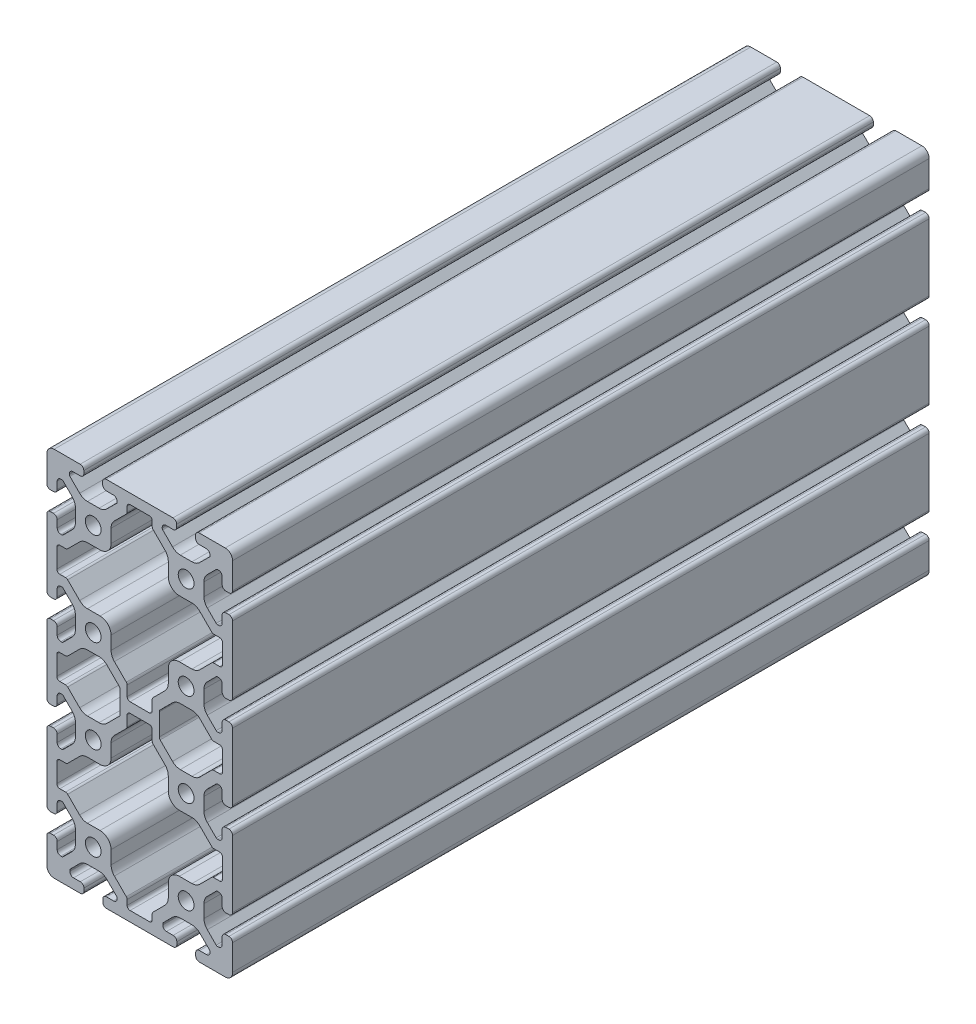
SolidWorks part; units mm, degrees
material "6105-T5 Aluminum"
ref_plane "Front Plane" through (0, 0, 0) normal (0, 0, 1) x (1, 0, 0)
ref_plane "Top Plane" through (0, 0, 0) normal (0, 1, 0) x (1, 0, 0)
ref_plane "Right Plane" through (0, 0, 0) normal (1, 0, 0) x (0, 0, -1)
sketch "Sketch1" plane through (0, 0, 0) normal (0, 0, 1) x (1, 0, 0)
  line L0 (-24.13, 57.84) -> (-15.87, 57.84)
  line L1 (-14.6, 56.57) -> (-14.6, 52.2333)
  line L2 (-14.228, 51.3353) -> (-9.1098, 46.2171)
  line L3 (-7.685, 42.7773) -> (-7.685, 37.065)
  line L4 (-2.935, 32.315) -> (2.5008, 32.315)
  line L5 (5.8595, 30.9238) -> (11.0113, 25.772)
  line L6 (11.9093, 25.4) -> (14.41, 25.4)
  line L7 (15.68, 24.13) -> (15.68, 15.87)
  line L8 (14.41, 14.6) -> (11.9093, 14.6)
  line L9 (11.0113, 14.228) -> (5.8595, 9.0762)
  line L10 (2.5008, 7.685) -> (-2.935, 7.685)
  line L11 (-7.685, 2.935) -> (-7.685, -2.7773)
  line L12 (-9.1098, -6.2171) -> (-14.228, -11.3353)
  line L13 (-14.6, -12.2334) -> (-14.6, -14.41)
  line L14 (-15.87, -15.68) -> (-24.13, -15.68)
  line L15 (-25.4, -14.41) -> (-25.4, -12.2334)
  line L16 (-25.772, -11.3353) -> (-30.8902, -6.2171)
  line L17 (-32.315, -2.7773) -> (-32.315, 2.935)
  line L18 (-37.065, 7.685) -> (-42.5008, 7.685)
  line L19 (-45.8595, 9.0762) -> (-51.0113, 14.228)
  line L20 (-51.9093, 14.6) -> (-54.41, 14.6)
  line L21 (-55.68, 15.87) -> (-55.68, 24.13)
  line L22 (-54.41, 25.4) -> (-51.9093, 25.4)
  line L23 (-51.0113, 25.772) -> (-45.8595, 30.9238)
  line L24 (-42.5008, 32.315) -> (-37.065, 32.315)
  line L25 (-32.315, 37.065) -> (-32.315, 42.7773)
  line L26 (-30.8902, 46.2171) -> (-25.772, 51.3353)
  line L27 (-25.4, 52.2333) -> (-25.4, 56.57)
  line L28 (-28.802, 54.4147) -> (-34.1405, 49.0762)
  line L29 (-37.4992, 47.685) -> (-42.5008, 47.685)
  line L30 (-45.8595, 49.0762) -> (-51.0113, 54.228)
  line L31 (-51.9093, 54.6) -> (-54.41, 54.6)
  line L32 (-55.68, 55.87) -> (-55.68, 64.13)
  line L33 (-54.41, 65.4) -> (-51.9093, 65.4)
  line L34 (-51.0113, 65.772) -> (-45.8595, 70.9238)
  line L35 (-42.5008, 72.315) -> (-37.4992, 72.315)
  line L36 (-34.1405, 70.9238) -> (-28.802, 65.5853)
  line L37 (-28.43, 64.6872) -> (-28.43, 55.3128)
  line L38 (-11.57, 55.3128) -> (-11.57, 64.6872)
  line L39 (-11.198, 65.5853) -> (-5.8595, 70.9238)
  line L40 (-2.5008, 72.315) -> (2.5008, 72.315)
  line L41 (5.8595, 70.9238) -> (11.0113, 65.772)
  line L42 (11.9093, 65.4) -> (14.41, 65.4)
  line L43 (15.68, 64.13) -> (15.68, 55.87)
  line L44 (14.41, 54.6) -> (11.9093, 54.6)
  line L45 (11.0113, 54.228) -> (5.8595, 49.0762)
  line L46 (2.5008, 47.685) -> (-2.5008, 47.685)
  line L47 (-5.8595, 49.0762) -> (-11.198, 54.4147)
  line L48 (-15.87, 62.16) -> (-24.13, 62.16)
  line L49 (-25.4, 63.43) -> (-25.4, 67.7667)
  line L50 (-25.772, 68.6647) -> (-30.8902, 73.7829)
  line L51 (-32.315, 77.2227) -> (-32.315, 82.935)
  line L52 (-37.065, 87.685) -> (-42.5008, 87.685)
  line L53 (-45.8595, 89.0762) -> (-51.0113, 94.228)
  line L54 (-51.9093, 94.6) -> (-54.41, 94.6)
  line L55 (-55.68, 95.87) -> (-55.68, 104.13)
  line L56 (-54.41, 105.4) -> (-51.9093, 105.4)
  line L57 (-51.0113, 105.772) -> (-45.8595, 110.9238)
  line L58 (-42.5008, 112.315) -> (-37.065, 112.315)
  line L59 (-32.315, 117.065) -> (-32.315, 122.7773)
  line L60 (-30.8902, 126.2171) -> (-25.772, 131.3353)
  line L61 (-25.4, 132.2333) -> (-25.4, 134.41)
  line L62 (-24.13, 135.68) -> (-15.87, 135.68)
  line L63 (-14.6, 134.41) -> (-14.6, 132.2333)
  line L64 (-14.228, 131.3353) -> (-9.1098, 126.2171)
  line L65 (-7.685, 122.7773) -> (-7.685, 117.065)
  line L66 (-2.935, 112.315) -> (2.5008, 112.315)
  line L67 (5.8595, 110.9238) -> (11.0113, 105.772)
  line L68 (11.9093, 105.4) -> (14.41, 105.4)
  line L69 (15.68, 104.13) -> (15.68, 95.87)
  line L70 (14.41, 94.6) -> (11.9093, 94.6)
  line L71 (11.0113, 94.228) -> (5.8595, 89.0762)
  line L72 (2.5008, 87.685) -> (-2.935, 87.685)
  line L73 (-7.685, 82.935) -> (-7.685, 77.2227)
  line L74 (-9.1098, 73.7829) -> (-14.228, 68.6647)
  line L75 (-14.6, 67.7667) -> (-14.6, 63.43)
  line L76 (18.43, 115.94) -> (17.0946, 115.94)
  line L77 (15.5246, 114.37) -> (15.5246, 111.285)
  line L78 (13.9546, 109.715) -> (13.4925, 109.715)
  line L79 (12.9551, 109.9376) -> (9.1098, 113.7829)
  line L80 (7.685, 117.2227) -> (7.685, 122.7773)
  line L81 (9.1098, 126.2171) -> (12.9551, 130.0624)
  line L82 (13.4925, 130.285) -> (13.9546, 130.285)
  line L83 (15.5246, 128.715) -> (15.5246, 125.63)
  line L84 (17.0946, 124.06) -> (18.43, 124.06)
  line L85 (20, 125.63) -> (20, 136.83)
  line L86 (16.83, 140) -> (5.63, 140)
  line L87 (4.06, 138.43) -> (4.06, 137.25)
  line L88 (5.63, 135.68) -> (8.7154, 135.68)
  line L89 (10.2854, 134.11) -> (10.2854, 133.6201)
  line L90 (9.947, 133.1637) -> (5.8595, 129.0762)
  line L91 (2.5008, 127.685) -> (-2.5008, 127.685)
  line L92 (-5.8595, 129.0762) -> (-10.0628, 133.2795)
  line L93 (-10.2854, 133.8169) -> (-10.2854, 134.11)
  line L94 (-8.7154, 135.68) -> (-5.63, 135.68)
  line L95 (-4.06, 137.25) -> (-4.06, 138.43)
  line L96 (-5.63, 140) -> (-34.37, 140)
  line L97 (-35.94, 138.43) -> (-35.94, 137.25)
  line L98 (-34.37, 135.68) -> (-31.2846, 135.68)
  line L99 (-29.7146, 134.11) -> (-29.7146, 133.6201)
  line L100 (-30.053, 133.1637) -> (-34.1405, 129.0762)
  line L101 (-37.4992, 127.685) -> (-42.5008, 127.685)
  line L102 (-45.8595, 129.0762) -> (-50.0628, 133.2795)
  line L103 (-50.2854, 133.8169) -> (-50.2854, 134.11)
  line L104 (-48.7154, 135.68) -> (-45.63, 135.68)
  line L105 (-44.06, 137.25) -> (-44.06, 138.43)
  line L106 (-45.63, 140) -> (-56.83, 140)
  line L107 (-60, 136.83) -> (-60, 125.63)
  line L108 (-58.43, 124.06) -> (-57.0946, 124.06)
  line L109 (-55.5246, 125.63) -> (-55.5246, 128.715)
  line L110 (-53.9546, 130.285) -> (-53.4925, 130.285)
  line L111 (-52.9551, 130.0624) -> (-49.1098, 126.2171)
  line L112 (-47.685, 122.7773) -> (-47.685, 117.2227)
  line L113 (-49.1098, 113.7829) -> (-52.9551, 109.9376)
  line L114 (-53.4925, 109.715) -> (-53.9546, 109.715)
  line L115 (-55.5246, 111.285) -> (-55.5246, 114.37)
  line L116 (-57.0946, 115.94) -> (-58.43, 115.94)
  line L117 (-60, 114.37) -> (-60, 85.63)
  line L118 (-58.43, 84.06) -> (-57.0946, 84.06)
  line L119 (-55.5246, 85.63) -> (-55.5246, 88.715)
  line L120 (-53.9546, 90.285) -> (-53.4925, 90.285)
  line L121 (-52.9551, 90.0624) -> (-49.1098, 86.2171)
  line L122 (-47.685, 82.7773) -> (-47.685, 77.2227)
  line L123 (-49.1098, 73.7829) -> (-52.9551, 69.9376)
  line L124 (-53.4925, 69.715) -> (-53.9546, 69.715)
  line L125 (-55.5246, 71.285) -> (-55.5246, 74.37)
  line L126 (-57.0946, 75.94) -> (-58.43, 75.94)
  line L127 (-60, 74.37) -> (-60, 45.63)
  line L128 (-58.43, 44.06) -> (-57.0946, 44.06)
  line L129 (-55.5246, 45.63) -> (-55.5246, 48.715)
  line L130 (-53.9546, 50.285) -> (-53.4925, 50.285)
  line L131 (-52.9551, 50.0624) -> (-49.1098, 46.2171)
  line L132 (-47.685, 42.7773) -> (-47.685, 37.2227)
  line L133 (-49.1098, 33.7829) -> (-52.9551, 29.9376)
  line L134 (-53.4925, 29.715) -> (-53.9546, 29.715)
  line L135 (-55.5246, 31.285) -> (-55.5246, 34.37)
  line L136 (-57.0946, 35.94) -> (-58.43, 35.94)
  line L137 (-60, 34.37) -> (-60, 5.63)
  line L138 (-58.43, 4.06) -> (-57.0946, 4.06)
  line L139 (-55.5246, 5.63) -> (-55.5246, 8.715)
  line L140 (-53.9546, 10.285) -> (-53.4925, 10.285)
  line L141 (-52.9551, 10.0624) -> (-49.1098, 6.2171)
  line L142 (-47.685, 2.7773) -> (-47.685, -2.7773)
  line L143 (-49.1098, -6.2171) -> (-52.9551, -10.0624)
  line L144 (-53.4925, -10.285) -> (-53.9546, -10.285)
  line L145 (-55.5246, -8.715) -> (-55.5246, -5.63)
  line L146 (-57.0946, -4.06) -> (-58.43, -4.06)
  line L147 (-60, -5.63) -> (-60, -16.83)
  line L148 (-56.83, -20) -> (-45.573, -20)
  line L149 (-44.003, -18.43) -> (-44.003, -17.25)
  line L150 (-45.573, -15.68) -> (-48.4757, -15.68)
  line L151 (-50.0447, -14.0552) -> (-50.033, -13.7199)
  line L152 (-49.8238, -13.0405) -> (-45.8595, -9.0762)
  line L153 (-42.5008, -7.685) -> (-37.4992, -7.685)
  line L154 (-34.1405, -9.0762) -> (-29.9372, -13.2795)
  line L155 (-29.7146, -13.8169) -> (-29.7146, -14.11)
  line L156 (-31.2846, -15.68) -> (-34.2421, -15.68)
  line L157 (-35.8795, -17.25) -> (-35.8796, -18.43)
  line L158 (-34.2421, -20) -> (-5.573, -20)
  line L159 (-4.003, -18.43) -> (-4.003, -17.25)
  line L160 (-5.573, -15.68) -> (-8.4757, -15.68)
  line L161 (-10.0447, -14.0552) -> (-10.033, -13.7199)
  line L162 (-9.8238, -13.0405) -> (-5.8595, -9.0762)
  line L163 (-2.5008, -7.685) -> (2.5008, -7.685)
  line L164 (5.8595, -9.0762) -> (10.0628, -13.2795)
  line L165 (10.2854, -13.8169) -> (10.2854, -14.11)
  line L166 (8.7154, -15.68) -> (5.7579, -15.68)
  line L167 (4.1204, -17.2515) -> (4.1204, -18.4315)
  line L168 (5.7579, -20) -> (17.0184, -20)
  line L169 (20, -16.6746) -> (20, -5.63)
  line L170 (18.43, -4.06) -> (17.0946, -4.06)
  line L171 (15.5246, -5.63) -> (15.5246, -8.715)
  line L172 (13.9546, -10.285) -> (13.4925, -10.285)
  line L173 (12.9551, -10.0624) -> (9.1098, -6.2171)
  line L174 (7.685, -2.7773) -> (7.685, 2.7773)
  line L175 (9.1098, 6.2171) -> (12.9551, 10.0624)
  line L176 (13.4925, 10.285) -> (13.9546, 10.285)
  line L177 (15.5246, 8.715) -> (15.5246, 5.63)
  line L178 (17.0946, 4.06) -> (18.43, 4.06)
  line L179 (20, 5.63) -> (20, 34.37)
  line L180 (18.43, 35.94) -> (17.0946, 35.94)
  line L181 (15.5246, 34.37) -> (15.5246, 31.285)
  line L182 (13.9546, 29.715) -> (13.4925, 29.715)
  line L183 (12.9551, 29.9376) -> (9.1098, 33.7829)
  line L184 (7.685, 37.2227) -> (7.685, 42.7773)
  line L185 (9.1098, 46.2171) -> (12.9551, 50.0624)
  line L186 (13.4925, 50.285) -> (13.9546, 50.285)
  line L187 (15.5246, 48.715) -> (15.5246, 45.63)
  line L188 (17.0946, 44.06) -> (18.43, 44.06)
  line L189 (20, 45.63) -> (20, 74.37)
  line L190 (18.43, 75.94) -> (17.0946, 75.94)
  line L191 (15.5246, 74.37) -> (15.5246, 71.285)
  line L192 (13.9546, 69.715) -> (13.4925, 69.715)
  line L193 (12.9551, 69.9376) -> (9.1098, 73.7829)
  line L194 (7.685, 77.2227) -> (7.685, 82.7773)
  line L195 (9.1098, 86.2171) -> (12.9551, 90.0624)
  line L196 (13.4925, 90.285) -> (13.9546, 90.285)
  line L197 (15.5246, 88.715) -> (15.5246, 85.63)
  line L198 (17.0946, 84.06) -> (18.43, 84.06)
  line L199 (20, 85.63) -> (20, 114.37)
  arc A0 (-14.6, 56.57) -> (-15.87, 57.84) centre (-15.87, 56.57) ccw
  arc A1 (-14.6, 52.2333) -> (-14.228, 51.3353) centre (-13.33, 52.2333) ccw
  arc A2 (-7.685, 42.7773) -> (-9.1098, 46.2171) centre (-12.5496, 42.7773) ccw
  arc A3 (-7.685, 37.065) -> (-2.935, 32.315) centre (-2.935, 37.065) ccw
  arc A4 (5.8595, 30.9238) -> (2.5008, 32.315) centre (2.5008, 27.565) ccw
  arc A5 (11.0113, 25.772) -> (11.9093, 25.4) centre (11.9093, 26.67) ccw
  arc A6 (15.68, 24.13) -> (14.41, 25.4) centre (14.41, 24.13) ccw
  arc A7 (14.41, 14.6) -> (15.68, 15.87) centre (14.41, 15.87) ccw
  arc A8 (11.9093, 14.6) -> (11.0113, 14.228) centre (11.9093, 13.33) ccw
  arc A9 (2.5008, 7.685) -> (5.8595, 9.0762) centre (2.5008, 12.435) ccw
  arc A10 (-2.935, 7.685) -> (-7.685, 2.935) centre (-2.935, 2.935) ccw
  arc A11 (-9.1098, -6.2171) -> (-7.685, -2.7773) centre (-12.5496, -2.7773) ccw
  arc A12 (-14.228, -11.3353) -> (-14.6, -12.2334) centre (-13.33, -12.2334) ccw
  arc A13 (-15.87, -15.68) -> (-14.6, -14.41) centre (-15.87, -14.41) ccw
  arc A14 (-25.4, -14.41) -> (-24.13, -15.68) centre (-24.13, -14.41) ccw
  arc A15 (-25.4, -12.2334) -> (-25.772, -11.3353) centre (-26.67, -12.2334) ccw
  arc A16 (-32.315, -2.7773) -> (-30.8902, -6.2171) centre (-27.4504, -2.7773) ccw
  arc A17 (-32.315, 2.935) -> (-37.065, 7.685) centre (-37.065, 2.935) ccw
  arc A18 (-45.8595, 9.0762) -> (-42.5008, 7.685) centre (-42.5008, 12.435) ccw
  arc A19 (-51.0113, 14.228) -> (-51.9093, 14.6) centre (-51.9093, 13.33) ccw
  arc A20 (-55.68, 15.87) -> (-54.41, 14.6) centre (-54.41, 15.87) ccw
  arc A21 (-54.41, 25.4) -> (-55.68, 24.13) centre (-54.41, 24.13) ccw
  arc A22 (-51.9093, 25.4) -> (-51.0113, 25.772) centre (-51.9093, 26.67) ccw
  arc A23 (-42.5008, 32.315) -> (-45.8595, 30.9238) centre (-42.5008, 27.565) ccw
  arc A24 (-37.065, 32.315) -> (-32.315, 37.065) centre (-37.065, 37.065) ccw
  arc A25 (-30.8902, 46.2171) -> (-32.315, 42.7773) centre (-27.4504, 42.7773) ccw
  arc A26 (-25.772, 51.3353) -> (-25.4, 52.2333) centre (-26.67, 52.2333) ccw
  arc A27 (-24.13, 57.84) -> (-25.4, 56.57) centre (-24.13, 56.57) ccw
  arc A28 (-28.802, 54.4147) -> (-28.43, 55.3128) centre (-29.7, 55.3128) ccw
  arc A29 (-37.4992, 47.685) -> (-34.1405, 49.0762) centre (-37.4992, 52.435) ccw
  arc A30 (-45.8595, 49.0762) -> (-42.5008, 47.685) centre (-42.5008, 52.435) ccw
  arc A31 (-51.0113, 54.228) -> (-51.9093, 54.6) centre (-51.9093, 53.33) ccw
  arc A32 (-55.68, 55.87) -> (-54.41, 54.6) centre (-54.41, 55.87) ccw
  arc A33 (-54.41, 65.4) -> (-55.68, 64.13) centre (-54.41, 64.13) ccw
  arc A34 (-51.9093, 65.4) -> (-51.0113, 65.772) centre (-51.9093, 66.67) ccw
  arc A35 (-42.5008, 72.315) -> (-45.8595, 70.9238) centre (-42.5008, 67.565) ccw
  arc A36 (-34.1405, 70.9238) -> (-37.4992, 72.315) centre (-37.4992, 67.565) ccw
  arc A37 (-28.43, 64.6872) -> (-28.802, 65.5853) centre (-29.7, 64.6872) ccw
  circle A38 centre (-40, 40) radius 3.4
  circle A39 centre (0, 40) radius 3.4
  circle A40 centre (-40, 120) radius 3.4
  circle A41 centre (0, 120) radius 3.4
  circle A42 centre (0, 80) radius 3.4
  circle A43 centre (-40, 80) radius 3.4
  circle A44 centre (0, 0) radius 3.4
  circle A45 centre (-40, 0) radius 3.4
  arc A46 (-11.198, 65.5853) -> (-11.57, 64.6872) centre (-10.3, 64.6872) ccw
  arc A47 (-2.5008, 72.315) -> (-5.8595, 70.9238) centre (-2.5008, 67.565) ccw
  arc A48 (5.8595, 70.9238) -> (2.5008, 72.315) centre (2.5008, 67.565) ccw
  arc A49 (11.0113, 65.772) -> (11.9093, 65.4) centre (11.9093, 66.67) ccw
  arc A50 (15.68, 64.13) -> (14.41, 65.4) centre (14.41, 64.13) ccw
  arc A51 (14.41, 54.6) -> (15.68, 55.87) centre (14.41, 55.87) ccw
  arc A52 (11.9093, 54.6) -> (11.0113, 54.228) centre (11.9093, 53.33) ccw
  arc A53 (2.5008, 47.685) -> (5.8595, 49.0762) centre (2.5008, 52.435) ccw
  arc A54 (-5.8595, 49.0762) -> (-2.5008, 47.685) centre (-2.5008, 52.435) ccw
  arc A55 (-11.57, 55.3128) -> (-11.198, 54.4147) centre (-10.3, 55.3128) ccw
  arc A56 (-15.87, 62.16) -> (-14.6, 63.43) centre (-15.87, 63.43) ccw
  arc A57 (-25.4, 63.43) -> (-24.13, 62.16) centre (-24.13, 63.43) ccw
  arc A58 (-25.4, 67.7667) -> (-25.772, 68.6647) centre (-26.67, 67.7667) ccw
  arc A59 (-32.315, 77.2227) -> (-30.8902, 73.7829) centre (-27.4504, 77.2227) ccw
  arc A60 (-32.315, 82.935) -> (-37.065, 87.685) centre (-37.065, 82.935) ccw
  arc A61 (-45.8595, 89.0762) -> (-42.5008, 87.685) centre (-42.5008, 92.435) ccw
  arc A62 (-51.0113, 94.228) -> (-51.9093, 94.6) centre (-51.9093, 93.33) ccw
  arc A63 (-55.68, 95.87) -> (-54.41, 94.6) centre (-54.41, 95.87) ccw
  arc A64 (-54.41, 105.4) -> (-55.68, 104.13) centre (-54.41, 104.13) ccw
  arc A65 (-51.9093, 105.4) -> (-51.0113, 105.772) centre (-51.9093, 106.67) ccw
  arc A66 (-42.5008, 112.315) -> (-45.8595, 110.9238) centre (-42.5008, 107.565) ccw
  arc A67 (-37.065, 112.315) -> (-32.315, 117.065) centre (-37.065, 117.065) ccw
  arc A68 (-30.8902, 126.2171) -> (-32.315, 122.7773) centre (-27.4504, 122.7773) ccw
  arc A69 (-25.772, 131.3353) -> (-25.4, 132.2333) centre (-26.67, 132.2333) ccw
  arc A70 (-24.13, 135.68) -> (-25.4, 134.41) centre (-24.13, 134.41) ccw
  arc A71 (-14.6, 134.41) -> (-15.87, 135.68) centre (-15.87, 134.41) ccw
  arc A72 (-14.6, 132.2333) -> (-14.228, 131.3353) centre (-13.33, 132.2333) ccw
  arc A73 (-7.685, 122.7773) -> (-9.1098, 126.2171) centre (-12.5496, 122.7773) ccw
  arc A74 (-7.685, 117.065) -> (-2.935, 112.315) centre (-2.935, 117.065) ccw
  arc A75 (5.8595, 110.9238) -> (2.5008, 112.315) centre (2.5008, 107.565) ccw
  arc A76 (11.0113, 105.772) -> (11.9093, 105.4) centre (11.9093, 106.67) ccw
  arc A77 (15.68, 104.13) -> (14.41, 105.4) centre (14.41, 104.13) ccw
  arc A78 (14.41, 94.6) -> (15.68, 95.87) centre (14.41, 95.87) ccw
  arc A79 (11.9093, 94.6) -> (11.0113, 94.228) centre (11.9093, 93.33) ccw
  arc A80 (2.5008, 87.685) -> (5.8595, 89.0762) centre (2.5008, 92.435) ccw
  arc A81 (-2.935, 87.685) -> (-7.685, 82.935) centre (-2.935, 82.935) ccw
  arc A82 (-9.1098, 73.7829) -> (-7.685, 77.2227) centre (-12.5496, 77.2227) ccw
  arc A83 (-14.228, 68.6647) -> (-14.6, 67.7667) centre (-13.33, 67.7667) ccw
  arc A84 (17.0946, 115.94) -> (15.5246, 114.37) centre (17.0946, 114.37) ccw
  arc A85 (13.9546, 109.715) -> (15.5246, 111.285) centre (13.9546, 111.285) ccw
  arc A86 (12.9551, 109.9376) -> (13.4925, 109.715) centre (13.4925, 110.475) ccw
  arc A87 (7.685, 117.2227) -> (9.1098, 113.7829) centre (12.5496, 117.2227) ccw
  arc A88 (9.1098, 126.2171) -> (7.685, 122.7773) centre (12.5496, 122.7773) ccw
  arc A89 (13.4925, 130.285) -> (12.9551, 130.0624) centre (13.4925, 129.525) ccw
  arc A90 (15.5246, 128.715) -> (13.9546, 130.285) centre (13.9546, 128.715) ccw
  arc A91 (15.5246, 125.63) -> (17.0946, 124.06) centre (17.0946, 125.63) ccw
  arc A92 (18.43, 124.06) -> (20, 125.63) centre (18.43, 125.63) ccw
  arc A93 (20, 136.83) -> (16.83, 140) centre (16.83, 136.83) ccw
  arc A94 (5.63, 140) -> (4.06, 138.43) centre (5.63, 138.43) ccw
  arc A95 (4.06, 137.25) -> (5.63, 135.68) centre (5.63, 137.25) ccw
  arc A96 (10.2854, 134.11) -> (8.7154, 135.68) centre (8.7154, 134.11) ccw
  arc A97 (9.947, 133.1637) -> (10.2854, 133.6201) centre (9.55, 133.8117) ccw
  arc A98 (2.5008, 127.685) -> (5.8595, 129.0762) centre (2.5008, 132.435) ccw
  arc A99 (-5.8595, 129.0762) -> (-2.5008, 127.685) centre (-2.5008, 132.435) ccw
  arc A100 (-10.2854, 133.8169) -> (-10.0628, 133.2795) centre (-9.5254, 133.8169) ccw
  arc A101 (-8.7154, 135.68) -> (-10.2854, 134.11) centre (-8.7154, 134.11) ccw
  arc A102 (-5.63, 135.68) -> (-4.06, 137.25) centre (-5.63, 137.25) ccw
  arc A103 (-4.06, 138.43) -> (-5.63, 140) centre (-5.63, 138.43) ccw
  arc A104 (-34.37, 140) -> (-35.94, 138.43) centre (-34.37, 138.43) ccw
  arc A105 (-35.94, 137.25) -> (-34.37, 135.68) centre (-34.37, 137.25) ccw
  arc A106 (-29.7146, 134.11) -> (-31.2846, 135.68) centre (-31.2846, 134.11) ccw
  arc A107 (-30.053, 133.1637) -> (-29.7146, 133.6201) centre (-30.45, 133.8117) ccw
  arc A108 (-37.4992, 127.685) -> (-34.1405, 129.0762) centre (-37.4992, 132.435) ccw
  arc A109 (-45.8595, 129.0762) -> (-42.5008, 127.685) centre (-42.5008, 132.435) ccw
  arc A110 (-50.2854, 133.8169) -> (-50.0628, 133.2795) centre (-49.5254, 133.8169) ccw
  arc A111 (-48.7154, 135.68) -> (-50.2854, 134.11) centre (-48.7154, 134.11) ccw
  arc A112 (-45.63, 135.68) -> (-44.06, 137.25) centre (-45.63, 137.25) ccw
  arc A113 (-44.06, 138.43) -> (-45.63, 140) centre (-45.63, 138.43) ccw
  arc A114 (-56.83, 140) -> (-60, 136.83) centre (-56.83, 136.83) ccw
  arc A115 (-60, 125.63) -> (-58.43, 124.06) centre (-58.43, 125.63) ccw
  arc A116 (-57.0946, 124.06) -> (-55.5246, 125.63) centre (-57.0946, 125.63) ccw
  arc A117 (-53.9546, 130.285) -> (-55.5246, 128.715) centre (-53.9546, 128.715) ccw
  arc A118 (-52.9551, 130.0624) -> (-53.4925, 130.285) centre (-53.4925, 129.525) ccw
  arc A119 (-47.685, 122.7773) -> (-49.1098, 126.2171) centre (-52.5496, 122.7773) ccw
  arc A120 (-49.1098, 113.7829) -> (-47.685, 117.2227) centre (-52.5496, 117.2227) ccw
  arc A121 (-53.4925, 109.715) -> (-52.9551, 109.9376) centre (-53.4925, 110.475) ccw
  arc A122 (-55.5246, 111.285) -> (-53.9546, 109.715) centre (-53.9546, 111.285) ccw
  arc A123 (-55.5246, 114.37) -> (-57.0946, 115.94) centre (-57.0946, 114.37) ccw
  arc A124 (-58.43, 115.94) -> (-60, 114.37) centre (-58.43, 114.37) ccw
  arc A125 (-60, 85.63) -> (-58.43, 84.06) centre (-58.43, 85.63) ccw
  arc A126 (-57.0946, 84.06) -> (-55.5246, 85.63) centre (-57.0946, 85.63) ccw
  arc A127 (-53.9546, 90.285) -> (-55.5246, 88.715) centre (-53.9546, 88.715) ccw
  arc A128 (-52.9551, 90.0624) -> (-53.4925, 90.285) centre (-53.4925, 89.525) ccw
  arc A129 (-47.685, 82.7773) -> (-49.1098, 86.2171) centre (-52.5496, 82.7773) ccw
  arc A130 (-49.1098, 73.7829) -> (-47.685, 77.2227) centre (-52.5496, 77.2227) ccw
  arc A131 (-53.4925, 69.715) -> (-52.9551, 69.9376) centre (-53.4925, 70.475) ccw
  arc A132 (-55.5246, 71.285) -> (-53.9546, 69.715) centre (-53.9546, 71.285) ccw
  arc A133 (-55.5246, 74.37) -> (-57.0946, 75.94) centre (-57.0946, 74.37) ccw
  arc A134 (-58.43, 75.94) -> (-60, 74.37) centre (-58.43, 74.37) ccw
  arc A135 (-60, 45.63) -> (-58.43, 44.06) centre (-58.43, 45.63) ccw
  arc A136 (-57.0946, 44.06) -> (-55.5246, 45.63) centre (-57.0946, 45.63) ccw
  arc A137 (-53.9546, 50.285) -> (-55.5246, 48.715) centre (-53.9546, 48.715) ccw
  arc A138 (-52.9551, 50.0624) -> (-53.4925, 50.285) centre (-53.4925, 49.525) ccw
  arc A139 (-47.685, 42.7773) -> (-49.1098, 46.2171) centre (-52.5496, 42.7773) ccw
  arc A140 (-49.1098, 33.7829) -> (-47.685, 37.2227) centre (-52.5496, 37.2227) ccw
  arc A141 (-53.4925, 29.715) -> (-52.9551, 29.9376) centre (-53.4925, 30.475) ccw
  arc A142 (-55.5246, 31.285) -> (-53.9546, 29.715) centre (-53.9546, 31.285) ccw
  arc A143 (-55.5246, 34.37) -> (-57.0946, 35.94) centre (-57.0946, 34.37) ccw
  arc A144 (-58.43, 35.94) -> (-60, 34.37) centre (-58.43, 34.37) ccw
  arc A145 (-60, 5.63) -> (-58.43, 4.06) centre (-58.43, 5.63) ccw
  arc A146 (-57.0946, 4.06) -> (-55.5246, 5.63) centre (-57.0946, 5.63) ccw
  arc A147 (-53.9546, 10.285) -> (-55.5246, 8.715) centre (-53.9546, 8.715) ccw
  arc A148 (-52.9551, 10.0624) -> (-53.4925, 10.285) centre (-53.4925, 9.525) ccw
  arc A149 (-47.685, 2.7773) -> (-49.1098, 6.2171) centre (-52.5496, 2.7773) ccw
  arc A150 (-49.1098, -6.2171) -> (-47.685, -2.7773) centre (-52.5496, -2.7773) ccw
  arc A151 (-53.4925, -10.285) -> (-52.9551, -10.0624) centre (-53.4925, -9.525) ccw
  arc A152 (-55.5246, -8.715) -> (-53.9546, -10.285) centre (-53.9546, -8.715) ccw
  arc A153 (-55.5246, -5.63) -> (-57.0946, -4.06) centre (-57.0946, -5.63) ccw
  arc A154 (-58.43, -4.06) -> (-60, -5.63) centre (-58.43, -5.63) ccw
  arc A155 (-60, -16.83) -> (-56.83, -20) centre (-56.83, -16.83) ccw
  arc A156 (-45.573, -20) -> (-44.003, -18.43) centre (-45.573, -18.43) ccw
  arc A157 (-44.003, -17.25) -> (-45.573, -15.68) centre (-45.573, -17.25) ccw
  arc A158 (-50.0447, -14.0552) -> (-48.4757, -15.68) centre (-48.4757, -14.11) ccw
  arc A159 (-49.8238, -13.0405) -> (-50.033, -13.7199) centre (-49.2864, -13.5779) ccw
  arc A160 (-42.5008, -7.685) -> (-45.8595, -9.0762) centre (-42.5008, -12.435) ccw
  arc A161 (-34.1405, -9.0762) -> (-37.4992, -7.685) centre (-37.4992, -12.435) ccw
  arc A162 (-29.7146, -13.8169) -> (-29.9372, -13.2795) centre (-30.4746, -13.8169) ccw
  arc A163 (-31.2846, -15.68) -> (-29.7146, -14.11) centre (-31.2846, -14.11) ccw
  arc A164 (-34.2421, -15.68) -> (-35.8795, -17.25) centre (-34.3096, -17.2485) ccw
  arc A165 (-35.8796, -18.43) -> (-34.2421, -20) centre (-34.3096, -18.4315) ccw
  arc A166 (-5.573, -20) -> (-4.003, -18.43) centre (-5.573, -18.43) ccw
  arc A167 (-4.003, -17.25) -> (-5.573, -15.68) centre (-5.573, -17.25) ccw
  arc A168 (-10.0447, -14.0552) -> (-8.4757, -15.68) centre (-8.4757, -14.11) ccw
  arc A169 (-9.8238, -13.0405) -> (-10.033, -13.7199) centre (-9.2864, -13.5779) ccw
  arc A170 (-2.5008, -7.685) -> (-5.8595, -9.0762) centre (-2.5008, -12.435) ccw
  arc A171 (5.8595, -9.0762) -> (2.5008, -7.685) centre (2.5008, -12.435) ccw
  arc A172 (10.2854, -13.8169) -> (10.0628, -13.2795) centre (9.5254, -13.8169) ccw
  arc A173 (8.7154, -15.68) -> (10.2854, -14.11) centre (8.7154, -14.11) ccw
  arc A174 (5.7579, -15.68) -> (4.1204, -17.2515) centre (5.6932, -17.2515) ccw
  arc A175 (4.1204, -18.4315) -> (5.7579, -20) centre (5.6904, -18.4315) ccw
  arc A176 (17.0184, -20) -> (20, -16.6746) centre (16.8341, -16.8354) ccw
  arc A177 (20, -5.63) -> (18.43, -4.06) centre (18.43, -5.63) ccw
  arc A178 (17.0946, -4.06) -> (15.5246, -5.63) centre (17.0946, -5.63) ccw
  arc A179 (13.9546, -10.285) -> (15.5246, -8.715) centre (13.9546, -8.715) ccw
  arc A180 (12.9551, -10.0624) -> (13.4925, -10.285) centre (13.4925, -9.525) ccw
  arc A181 (7.685, -2.7773) -> (9.1098, -6.2171) centre (12.5496, -2.7773) ccw
  arc A182 (9.1098, 6.2171) -> (7.685, 2.7773) centre (12.5496, 2.7773) ccw
  arc A183 (13.4925, 10.285) -> (12.9551, 10.0624) centre (13.4925, 9.525) ccw
  arc A184 (15.5246, 8.715) -> (13.9546, 10.285) centre (13.9546, 8.715) ccw
  arc A185 (15.5246, 5.63) -> (17.0946, 4.06) centre (17.0946, 5.63) ccw
  arc A186 (18.43, 4.06) -> (20, 5.63) centre (18.43, 5.63) ccw
  arc A187 (20, 34.37) -> (18.43, 35.94) centre (18.43, 34.37) ccw
  arc A188 (17.0946, 35.94) -> (15.5246, 34.37) centre (17.0946, 34.37) ccw
  arc A189 (13.9546, 29.715) -> (15.5246, 31.285) centre (13.9546, 31.285) ccw
  arc A190 (12.9551, 29.9376) -> (13.4925, 29.715) centre (13.4925, 30.475) ccw
  arc A191 (7.685, 37.2227) -> (9.1098, 33.7829) centre (12.5496, 37.2227) ccw
  arc A192 (9.1098, 46.2171) -> (7.685, 42.7773) centre (12.5496, 42.7773) ccw
  arc A193 (13.4925, 50.285) -> (12.9551, 50.0624) centre (13.4925, 49.525) ccw
  arc A194 (15.5246, 48.715) -> (13.9546, 50.285) centre (13.9546, 48.715) ccw
  arc A195 (15.5246, 45.63) -> (17.0946, 44.06) centre (17.0946, 45.63) ccw
  arc A196 (18.43, 44.06) -> (20, 45.63) centre (18.43, 45.63) ccw
  arc A197 (20, 74.37) -> (18.43, 75.94) centre (18.43, 74.37) ccw
  arc A198 (17.0946, 75.94) -> (15.5246, 74.37) centre (17.0946, 74.37) ccw
  arc A199 (13.9546, 69.715) -> (15.5246, 71.285) centre (13.9546, 71.285) ccw
  arc A200 (12.9551, 69.9376) -> (13.4925, 69.715) centre (13.4925, 70.475) ccw
  arc A201 (7.685, 77.2227) -> (9.1098, 73.7829) centre (12.5496, 77.2227) ccw
  arc A202 (9.1098, 86.2171) -> (7.685, 82.7773) centre (12.5496, 82.7773) ccw
  arc A203 (13.4925, 90.285) -> (12.9551, 90.0624) centre (13.4925, 89.525) ccw
  arc A204 (15.5246, 88.715) -> (13.9546, 90.285) centre (13.9546, 88.715) ccw
  arc A205 (15.5246, 85.63) -> (17.0946, 84.06) centre (17.0946, 85.63) ccw
  arc A206 (18.43, 84.06) -> (20, 85.63) centre (18.43, 85.63) ccw
  arc A207 (20, 114.37) -> (18.43, 115.94) centre (18.43, 114.37) ccw
extrude "Extrude1" add sketch "Sketch1" against normal blind 300
